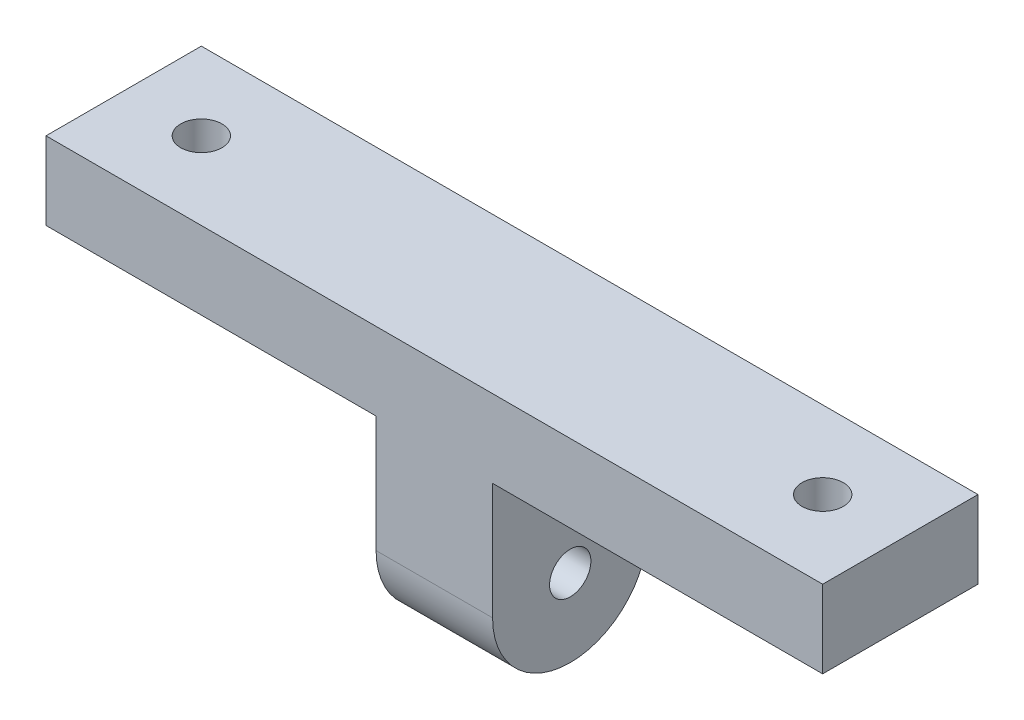
SolidWorks part; units mm, degrees
ref_plane "Front Plane" through (0, 0, 0) normal (0, 0, 1) x (1, 0, 0)
ref_plane "Top Plane" through (0, 0, 0) normal (0, 1, 0) x (1, 0, 0)
ref_plane "Right Plane" through (0, 0, 0) normal (1, 0, 0) x (0, 0, -1)
sketch "Sketch1" plane through (0, 0, 0) normal (0, 1, 0) x (1, 0, 0)
  line L1 (-63.5, 12.7) -> (63.5, 12.7)
  line L2 (-63.5, 12.7) -> (-63.5, -12.7)
  line L3 (-63.5, -12.7) -> (63.5, -12.7)
  line L4 (63.5, 12.7) -> (63.5, -12.7)
  line L5 (-63.5, 12.7) -> (63.5, -12.7) construction
  line L6 (-63.5, -12.7) -> (63.5, 12.7) construction
  line L8 (-50.8, 12.7) -> (-50.8, -12.7) construction
  line L9 (50.8, 12.7) -> (50.8, -12.7) construction
  line L10 (-9.525, 12.7) -> (-9.525, -12.7)
  line L11 (9.525, 12.7) -> (9.525, -12.7)
  line L12 (-63.5, 0) -> (63.5, 0)
  circle A0 centre (-50.8, 0) radius 3.3782
  circle A1 centre (50.8, 0) radius 3.3782
  point P0 (0, 0)
  point P6 (0, 0)
  point P7 (0, 0)
  point P8 (-28.9464, 0)
  point P9 (0, 0)
  point P18 (21.2908, 0)
  point P19 (0, 0)
  point P28 (0, 0)
  dimension "D7" = 6.7564
  dimension "D1" = 127
  dimension "D2" = 25.4
  dimension "D4" = 12.7
  dimension "D5" = 12.7
  dimension "D8" = 53.975
  dimension "D9" = 53.975
extrude "Boss-Extrude1" add sketch "Sketch1" along normal blind 12.7 contours A1 L12 L4 L1 L11 | A1 L12 L11 L3 L4 | L12 L10 L3 L11 | L10 L12 L11 L1 | A0 L12 L2 L3 L10 | A0 L12 L10 L1 L2 region at (-36.1288, 0, -6.482) region at (0, 0, -6.35) region at (-36.1288, 0, 6.482) region at (36.1288, 0, -6.482) region at (0, 0, 6.35) region at (36.1288, 0, 6.482)
extrude "Boss-Extrude2" add sketch "Sketch1<3>" against normal blind 31.75 contours L12 L10 L3 L11 | L10 L12 L11 L1 region at (0, 0, -6.35) region at (0, 0, 6.35)
sketch "Sketch1<3>" plane through (0, 0, 0) normal (0, 1, 0) x (1, 0, 0) same geometry as "Sketch1"
sketch "Sketch2" plane through (-9.525, 0, 0) normal (-1, 0, 0) x (0, 0, 1)
  line L0 (-12.7, -31.75) -> (12.7, -31.75) construction
  line L1 (0, 0) -> (0, -31.75) construction
  line L2 (-12.7, 0) -> (12.7, 0) construction
  circle A0 centre (0, -19.05) radius 3.3782
  dimension "D2" = 6.7564
  dimension "D1" = 12.7
extrude "Cut-Extrude1" cut sketch "Sketch2" against normal through all contours A0 L1 | L1 A0 region at (-9.525, -19.05, 1.4338) region at (-9.525, -19.05, -1.4338)
fillet "Fillet1" radius 12.7 2 edges at (0, -31.75, -12.7) (0, -31.75, 12.7)
